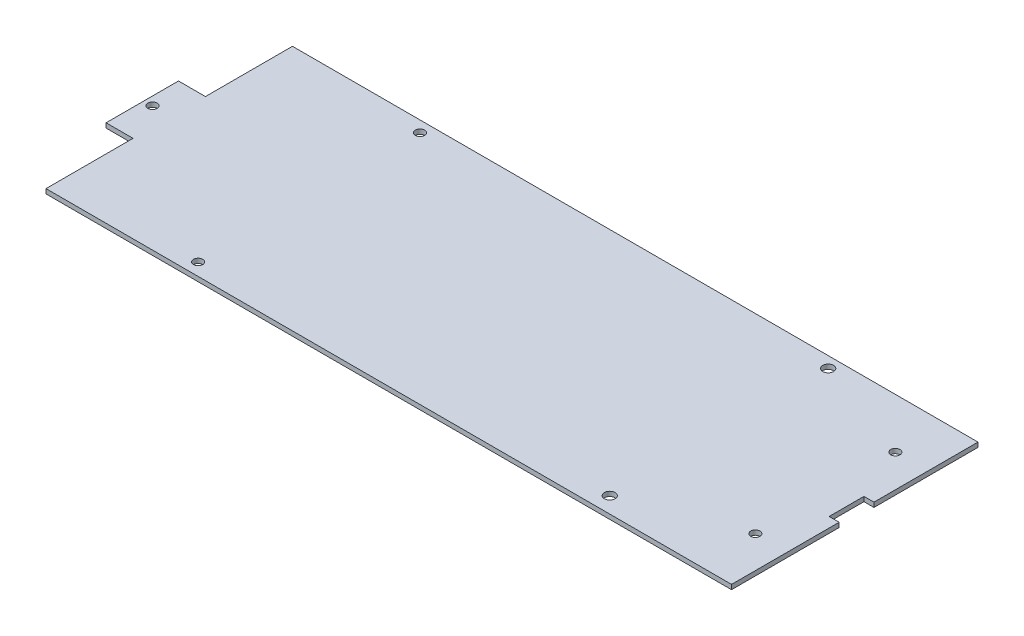
SolidWorks part; units mm, degrees
ref_plane "Front Plane" through (0, 0, 0) normal (0, 0, 1) x (1, 0, 0)
ref_plane "Top Plane" through (0, 0, 0) normal (0, 1, 0) x (1, 0, 0)
ref_plane "Right Plane" through (0, 0, 0) normal (1, 0, 0) x (0, 0, -1)
sketch "Sketch1" plane through (0, 0, 0) normal (0, 1, 0) x (1, 0, 0)
  line L0 (-302.2355, 23.5) -> (-284.7355, 23.5)
  line L1 (-284.7355, 80) -> (160.2645, 80)
  line L2 (-284.7355, 80) -> (-284.7355, 23.5)
  line L5 (-296.7465, -73.7679) -> (-296.7465, 76.0921) construction
  line L6 (-284.7355, 80) -> (-286.6881, 66.0337) construction
  line L7 (-302.2355, 23.5) -> (-302.2355, -23.5)
  line L8 (-302.2355, -23.5) -> (-284.7355, -23.5)
  line L9 (-284.7355, -23.5) -> (-284.7355, -80)
  line L10 (-284.7355, 31.0446) -> (-284.7355, 23.5) construction
  line L11 (160.2645, 80) -> (160.2645, 12.4621)
  line L12 (160.2645, 12.4621) -> (153.7645, 12.4621)
  line L13 (-302.2355, 0) -> (-26.2365, 1.1621) construction
  line L14 (161.6735, 9.4621) -> (169.6735, 9.4621) construction
  line L15 (153.7645, 12.4621) -> (153.7645, -10.1379)
  line L16 (153.7645, -10.1379) -> (160.2645, -10.1379)
  line L17 (169.6735, -7.1379) -> (161.6735, -7.1379) construction
  line L18 (160.2645, -10.1379) -> (160.2645, -80)
  line L19 (160.2645, -80) -> (-284.7355, -80)
  line L20 (-194.7355, 72.7736) -> (70.2645, 72.7736) construction
  circle A0 centre (-296.7465, 1.1621) radius 3
  circle A1 centre (-194.7355, 72.7736) radius 3
  circle A2 centre (70.2645, 72.7736) radius 3.5
  circle A3 centre (70.8641, -69.6342) radius 3.5
  circle A4 centre (-194.1265, -71.8658) radius 3
  circle A5 centre (139.1024, 47.5) radius 3
  circle A6 centre (139.4867, -43.7819) radius 3
  point P4 (0, 0)
  dimension "D9" = 6.5
  dimension "D12" = 6
  dimension "D3" = 6
  dimension "D15" = 6
  dimension "D16" = 7
  dimension "D1" = 56.5
  dimension "D2" = 56.5
  dimension "D4" = 3
  dimension "D5" = 3
  dimension "D6" = 17.5
  dimension "D7" = 445
  dimension "D8" = 69.8621
  dimension "D10" = 160
  dimension "D11" = 67.5379
  dimension "D13" = 90
  dimension "D14" = 90
  dimension "D17" = 32.5
extrude "Boss-Extrude1" add sketch "Sketch1" along normal blind 3 from offset 2 contours L8 L9 L1 L2 L0 L7 region at (-65.4442, 0, 0.0063)
